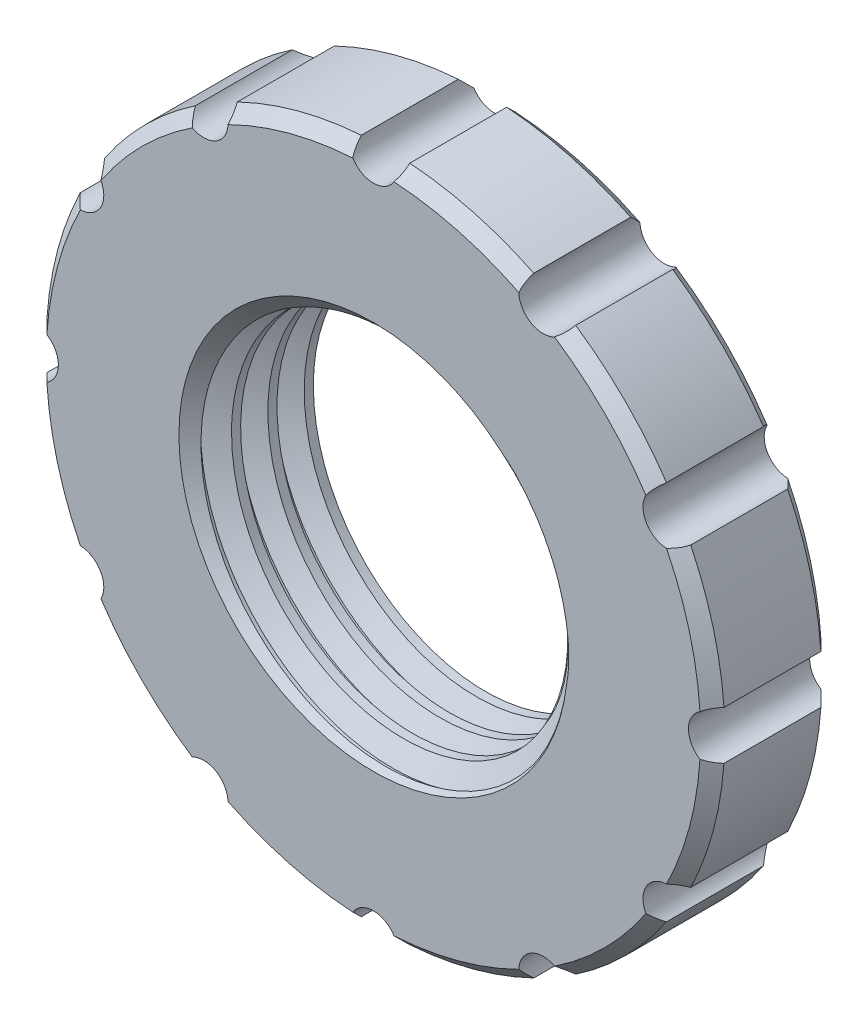
SolidWorks part; units mm, degrees
ref_plane "Front" through (0, 0, 0) normal (0, 0, 1) x (1, 0, 0)
ref_plane "Top" through (0, 0, 0) normal (0, 1, 0) x (1, 0, 0)
ref_plane "Right" through (0, 0, 0) normal (1, 0, 0) x (0, 0, -1)
other "Configuration Table"
sketch "Sketch1" plane through (0, 0, 0) normal (0, 0, 1) x (1, 0, 0)
  circle A0 centre (0, 0) radius 14
  dimension "D1" = 28
extrude "Boss-Extrude1" add sketch "Sketch1" along normal blind 5
chamfer "Chamfer1" distance 0.5 angle 45 1 edges at (14, 0, 0)
chamfer "Chamfer3" distance 0.5 angle 45 1 edges at (14, 0, 5)
sketch "Sketch6" plane through (0, 0, 5) normal (0, 0, 1) x (1, 0, 0)
  circle A0 centre (0, 14) radius 1
  circle A1 centre (0, 0) radius 14 construction
  circle A2 centre (7, 12.1244) radius 1
  circle A3 centre (12.1244, 7) radius 1
  circle A4 centre (14, 0) radius 1
  circle A5 centre (12.1244, -7) radius 1
  circle A6 centre (7, -12.1244) radius 1
  circle A7 centre (0, -14) radius 1
  circle A8 centre (-7, -12.1244) radius 1
  circle A9 centre (-12.1244, -7) radius 1
  circle A10 centre (-14, 0) radius 1
  circle A11 centre (-12.1244, 7) radius 1
  circle A12 centre (-7, 12.1244) radius 1
  point P4 (0, 0)
  point P29 (0, 0)
  dimension "D1" = 2
  dimension "D2" = 12
extrude "Cut-Extrude2" cut sketch "Sketch6" against normal through all
sketch "Sketch8" plane through (0, 0, 0) normal (0, 0, -1) x (-1, 0, 0)
  circle A0 centre (0, 0) radius 9
  circle A1 centre (0, 0) radius 11.25
  dimension "D1" = 18
  dimension "D2" = 22.5
extrude "Cut-Extrude3" cut sketch "Sketch8" against normal blind 1
hole_wizard "M16x1.5 Tapped Hole1" positions "Sketch9" profile "Sketch10" tap size "M16x1.5" standard "ANSI Metric" end condition up to next
sketch "Sketch9" plane through (0, 0, 5) normal (0, 0, 1) x (1, 0, 0)
  point P0 (0, 0)
sketch "Sketch10" plane through (0, 0, 5) normal (1, 0, 0) x (0, -1, 0)
  line L0 (0, 0) -> (0, 5)
  line L1 (0, 5) -> (7.25, 5)
  line L2 (7.25, 5) -> (7.25, 0.775)
  line L3 (7.25, 0.775) -> (8.025, 0)
  line L5 (8.025, 0) -> (0, 0)
  line L6 (-7.25, 0.775) -> (-8.025, 0) construction
  line L11 (0, -6.35) -> (0, 107.95) construction
  dimension "Thru Tap Drill Dia." = 14.5
  dimension "Thru Tap Drill Depth" = 5
  dimension "Near C'Sink Dia." = 16.05
  dimension "Near C'Sink Angle" = 90
thread "Thread2" pitch 1.5 method cut profile "Thread Profile2" start angle 0, offset 2, length 8, pitch 1.5, diameter 14.5
ref_plane "Plane2" through (-7.25, 0, 6.225) normal (0, -1, 0) x (-1, 0, 0)
sketch "Thread Profile2" plane through (-7.25, 0, 6.225) normal (0, -1, 0) x (-1, 0, 0)
  line L0 (0, 0) -> (0, 1.5) construction
  line L1 (0, 0) -> (0.8119, 0.4687)
  line L2 (0.8119, 0.4687) -> (0.8119, 0.6562)
  line L3 (0.8119, 0.6562) -> (0, 1.125)
  line L4 (0.8119, 0.5625) -> (0, 0.5625) construction
  line L11 (0, 0) -> (0, 1.125)
  point P2 (0, 0)
  dimension "Pitch" = 1.5
  dimension "Profile_Angle" = 60
  dimension "Profile_Land" = 0.1875
  dimension "Profile_Height" = 0.8119
